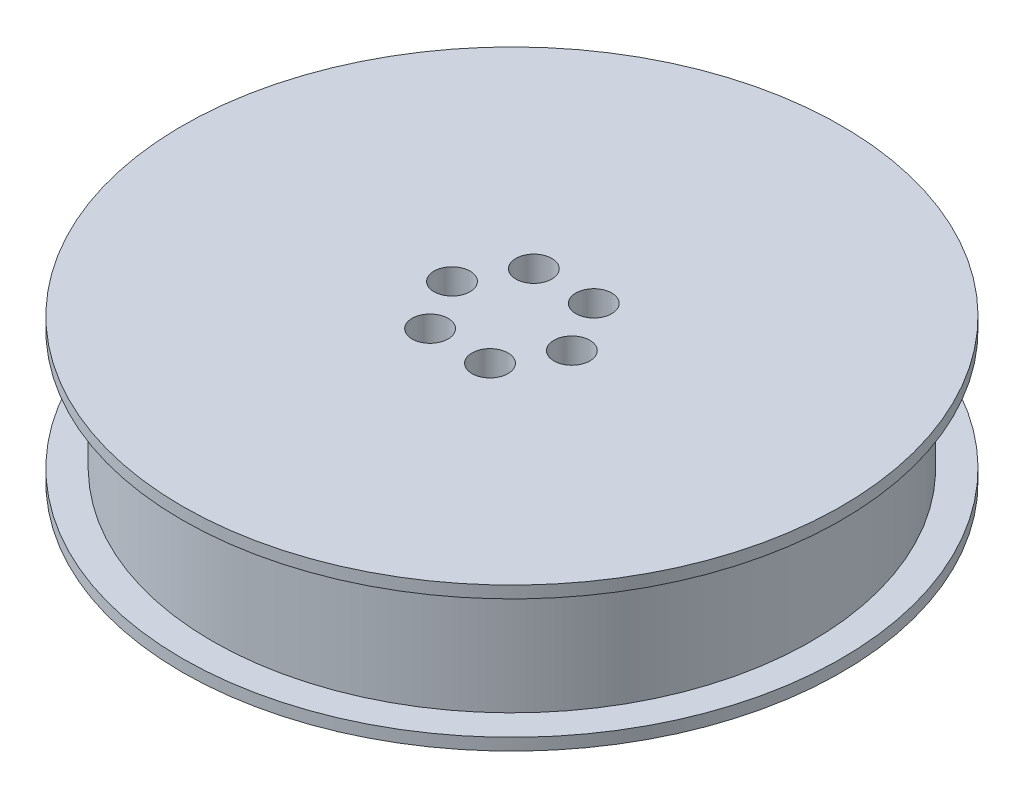
SolidWorks part; units mm, degrees
material "PETG"
ref_plane "Front Plane" through (0, 0, 0) normal (0, 0, 1) x (1, 0, 0)
ref_plane "Top Plane" through (0, 0, 0) normal (0, 1, 0) x (1, 0, 0)
ref_plane "Right Plane" through (0, 0, 0) normal (1, 0, 0) x (0, 0, -1)
sketch "Sketch1" plane through (0, 0, 0) normal (0, 1, 0) x (1, 0, 0)
  circle A0 centre (0, 0) radius 50
  dimension "D1" = 100
extrude "Boss-Extrude1" add sketch "Sketch1" along normal mid plane 20
sketch "Sketch2" plane through (0, 10, 0) normal (0, 1, 0) x (1, 0, 0)
  circle A0 centre (0, 0) radius 55
  dimension "D1" = 110
extrude "Boss-Extrude2" add sketch "Sketch2" along normal blind 2
mirror "Mirror1" about plane through (0, 0, 0) normal (0, 1, 0) of "Boss-Extrude2"
sketch "Sketch3" plane through (0, 12, 0) normal (0, 1, 0) x (1, 0, 0)
  line L0 (0, 0) -> (10, 0) construction
  circle A0 centre (10, 0) radius 1.7
  circle A1 centre (5, -8.6603) radius 1.7
  circle A2 centre (-5, -8.6603) radius 1.7
  circle A3 centre (-10, 0) radius 1.7
  circle A4 centre (-5, 8.6603) radius 1.7
  circle A5 centre (5, 8.6603) radius 1.7
  dimension "D1" = 10
  dimension "D2" = 3.4
  dimension "D3" = 6
extrude "Cut-Extrude1" cut sketch "Sketch3" against normal through all
sketch "Sketch4" plane through (0, 12, 0) normal (0, 1, 0) x (1, 0, 0)
  line L0 (0, 0) -> (5, -8.6603) construction
  circle A0 centre (5, -8.6603) radius 3
  circle A1 centre (-5, -8.6603) radius 3
  circle A2 centre (-10, 0) radius 3
  circle A3 centre (-5, 8.6603) radius 3
  circle A4 centre (5, 8.6603) radius 3
  circle A5 centre (10, 0) radius 3
  dimension "D1" = 6
  dimension "D2" = 6
extrude "Cut-Extrude2" cut sketch "Sketch4" against normal offset from surface (14 mm away) 10 up to face at (10, -12, 1.7)
equation "\"pitch_dia\"= 100mm"
equation "\"D1@Sketch1\"=\"pitch_dia\""
equation "\"D1@Sketch2\"=\"pitch_dia\"+10.00mm"
equation "\"belt_width\"= 20mm"
equation "\"D1@Boss-Extrude1\"=\"belt_width\""
